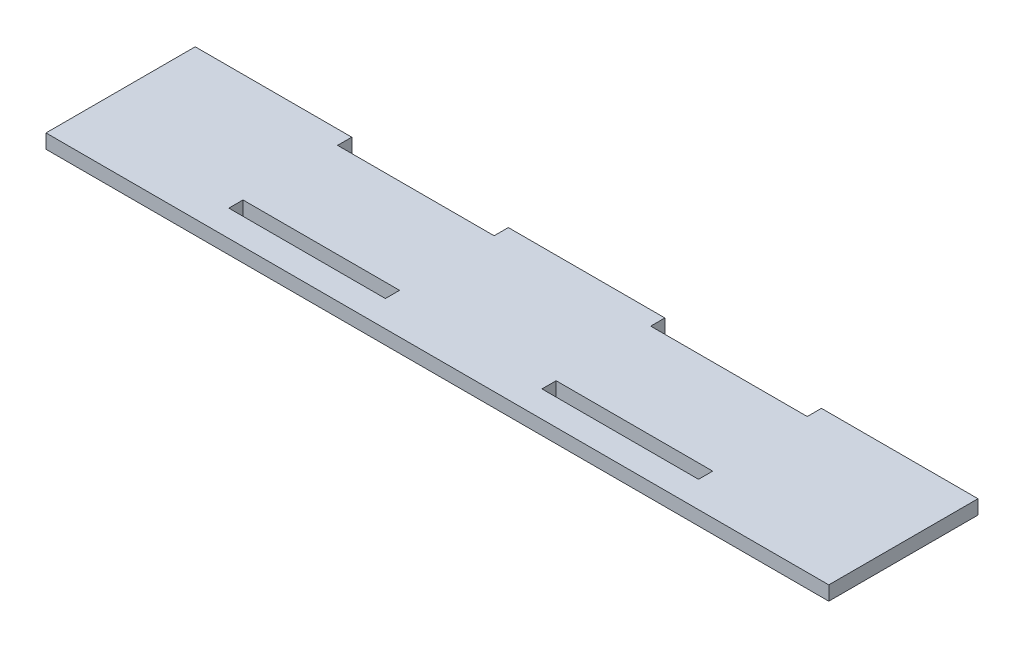
SolidWorks part; units mm, degrees
ref_plane "Front Plane" through (0, 0, 0) normal (0, 0, 1) x (1, 0, 0)
ref_plane "Top Plane" through (0, 0, 0) normal (0, 1, 0) x (1, 0, 0)
ref_plane "Right Plane" through (0, 0, 0) normal (1, 0, 0) x (0, 0, -1)
sketch "Sketch1" plane through (0, 0, 0) normal (0, 1, 0) x (1, 0, 0)
  line L0 (-44.7, -9.2) -> (-14.9, -9.2)
  line L1 (-74.5, -14.2) -> (74.5, -14.2)
  line L2 (-74.5, -14.2) -> (-74.5, 14.2)
  line L3 (-74.5, 14.2) -> (-44.7, 14.2)
  line L4 (74.5, -14.2) -> (74.5, 14.2)
  line L5 (14.9, -9.2) -> (44.7, -9.2)
  line L6 (-44.7, 11.5) -> (-14.9, 11.5)
  line L8 (-14.9, 14.2) -> (14.9, 14.2)
  line L10 (44.7, 14.2) -> (74.5, 14.2)
  line L11 (-44.7, -6.5) -> (-14.9, -6.5)
  line L14 (14.9, -6.5) -> (44.7, -6.5)
  line L16 (-44.7, 14.2) -> (-44.7, 11.5)
  line L17 (-14.9, 14.2) -> (-14.9, 11.5)
  line L18 (14.9, 14.2) -> (14.9, 11.5)
  line L19 (44.7, 14.2) -> (44.7, 11.5)
  line L20 (44.7, -6.5) -> (44.7, -9.2)
  line L21 (14.9, -6.5) -> (14.9, -9.2)
  line L22 (-14.9, -6.5) -> (-14.9, -9.2)
  line L23 (-44.7, -6.5) -> (-44.7, -9.2)
  line L25 (14.9, 11.5) -> (44.7, 11.5)
  point P0 (0, 0)
  dimension "D1" = 149
  dimension "D2" = 28.4
  dimension "D3" = 5
extrude "Boss-Extrude1" add sketch "Sketch1" along normal blind 2.7
